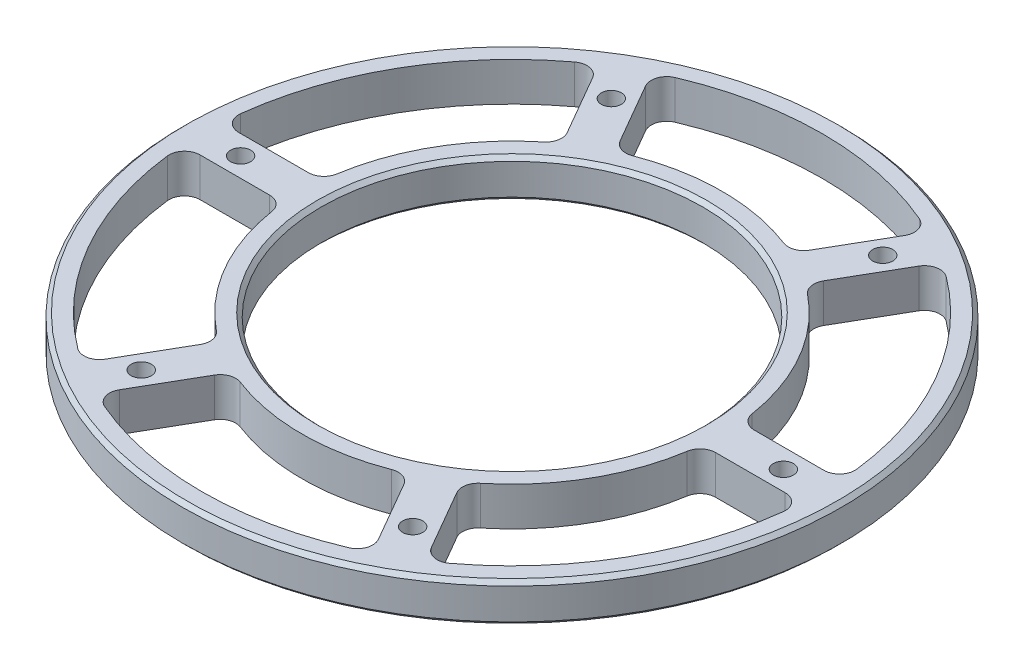
SolidWorks part; units mm, degrees
ref_plane "Front Plane" through (0, 0, 0) normal (0, 0, 1) x (1, 0, 0)
ref_plane "Top Plane" through (0, 0, 0) normal (0, 1, 0) x (1, 0, 0)
ref_plane "Right Plane" through (0, 0, 0) normal (1, 0, 0) x (0, 0, -1)
sketch "Sketch2" plane through (0, 0, 0) normal (1, 0, 0) x (0, 0, -1)
  line L0 (-49.2125, 0) -> (-84.9998, 0)
  line L1 (-84.9998, 0) -> (-84.9998, 10)
  line L2 (-84.9998, 10) -> (-49.2125, 10)
  line L3 (-49.2125, 10) -> (-49.2125, 0)
  dimension "D1" = 84.9998
  dimension "D2" = 10
  dimension "D4" = 49.2125
ref_axis "Axis1" through (0, -0.5, 0) along (0, 1, 0)
revolve "Revolve1" add sketch "Sketch2" angle 360 about axis through (0, -0.5, 0) along (0, 1, 0)
hole_wizard "#6 (0.204) Diameter Hole1" positions "Sketch6" profile "Sketch7" hole size "#6" standard "ANSI Inch" end condition through all
sketch "Sketch6" plane through (0, 10, 0) normal (0, 1, 0) x (1, 0, 0)
  line L0 (0, 0) -> (-69.8201, 120.932) construction
  line L2 (0, 0) -> (0, 109.0908) construction
  point P0 (-35, 60.6218)
  dimension "D1" = 30
  dimension "D2" = 70
sketch "Sketch7" plane through (-35, 10, -60.6218) normal (1, 0, 0) x (0, 0, 1)
  line L0 (0, 0) -> (0, 10)
  line L1 (0, 10) -> (2.5908, 10)
  line L2 (2.5908, 10) -> (2.5908, 0)
  line L5 (2.5908, 0) -> (0, 0)
  line L11 (0, -6.35) -> (0, 107.95) construction
  dimension "Thru Hole Dia." = 5.1816
  dimension "Thru Hole Depth" = 10
pattern_circular "CirPattern3" count 6 over 360 about axis through (0, -0.5, 0) along (0, 1, 0) of "#6 (0.204) Diameter Hole1"
sketch "Sketch8" plane through (0, 10, 0) normal (0, 1, 0) x (1, 0, 0)
  line L4 (0, 0) -> (0, 93.9995) construction
  line L5 (-22.6606, 49.2493) -> (-35.5916, 71.6464)
  line L6 (22.6606, 49.2493) -> (35.5916, 71.6464)
  line L7 (0, 0) -> (-35, 60.6218) construction
  arc A0 (-22.6606, 49.2493) -> (22.6606, 49.2493) centre (0, 0) cw
  arc A1 (-35.5916, 71.6464) -> (35.5916, 71.6464) centre (0, 0) cw
  circle A2 centre (0, 0) radius 84.9998 construction
  circle A4 centre (0, 0) radius 49.2125 construction
  dimension "D1" = 5
  dimension "D2" = 5
  dimension "D3" = 5
extrude "Cut-Extrude1" cut sketch "Sketch8" against normal through all
fillet "Fillet1" radius 4 4 edges at (-22.6606, 5, -49.2493) (22.6606, 5, -49.2493) (35.5916, 5, -71.6464) (-35.5916, 5, -71.6464)
pattern_circular "CirPattern4" count 6 over 360 about axis through (0, -0.5, 0) along (0, 1, 0) of "Cut-Extrude1", "Fillet1"
chamfer "Chamfer1" distance 1 angle 45 2 edges at (0, 10, -49.2125) (0, 0, -49.2125)
chamfer "Chamfer2" distance 1 angle 45 2 edges at (0, 10, -84.9998) (0, 0, -84.9998)
equation "\"TubeDiameter\" = 6.6929in"
equation "\"D1@Sketch2\"=\"TubeDiameter\"/2"
